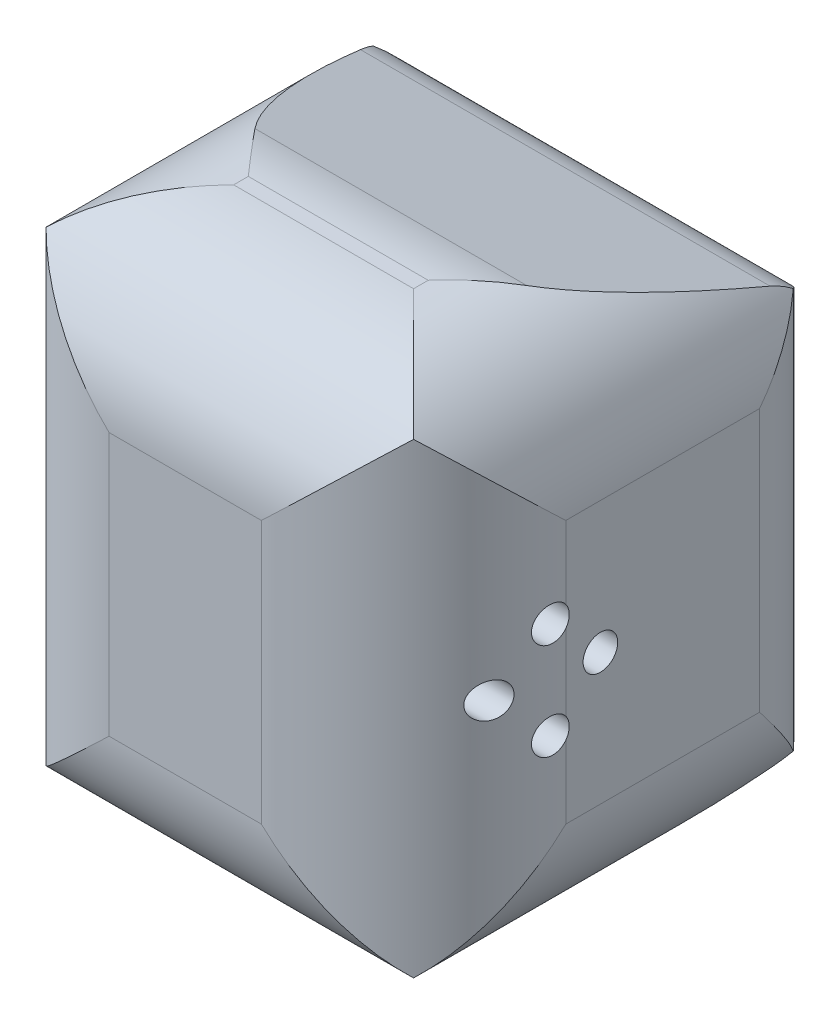
SolidWorks part; units mm, degrees
ref_plane "Front Plane" through (0, 0, 0) normal (0, 0, 1) x (1, 0, 0)
ref_plane "Top Plane" through (0, 0, 0) normal (0, 1, 0) x (1, 0, 0)
ref_plane "Right Plane" through (0, 0, 0) normal (1, 0, 0) x (0, 0, -1)
ref_plane "PX_m33_000" through (-33, 0, 0) normal (1, 0, 0) x (0, 0, -1)
sketch "S_prism1" plane through (-33, 0, 0) normal (1, 0, 0) x (0, 0, -1)
  line L0 (0, -20.5991) -> (0, 20.5991)
  line L1 (-7.0778, 30.1627) -> (-32.2859, 37.8651)
  line L2 (-39.8836, 39) -> (-42, 39)
  line L3 (-62, 19) -> (-62, -19)
  line L4 (-42, -39) -> (-39.8836, -39)
  line L5 (-32.2859, -37.8651) -> (-7.0778, -30.1627)
  arc A0 (-7.0778, -30.1627) -> (0, -20.5991) centre (-10.0001, -20.5991) ccw
  arc A1 (0, 20.5991) -> (-7.0778, 30.1627) centre (-10.0001, 20.5991) ccw
  arc A2 (-32.2859, 37.8651) -> (-39.8836, 39) centre (-39.8837, 12.9999) ccw
  arc A3 (-42, 39) -> (-62, 19) centre (-41.9999, 18.9999) ccw
  arc A4 (-62, -19) -> (-42, -39) centre (-41.9999, -18.9999) ccw
  arc A5 (-39.8836, -39) -> (-32.2859, -37.8651) centre (-39.8837, -12.9999) ccw
extrude "Boss_1" add sketch "S_prism1" along normal blind 66
ref_plane "PY_m40_000" through (0, -40, 0) normal (0, 1, 0) x (1, 0, 0)
sketch "S_pcut2" plane through (0, -40, 0) normal (0, 1, 0) x (1, 0, 0)
  line L0 (33.6, -62.6) -> (11, -62.6)
  line L1 (11, -62.6) -> (11, -62)
  line L2 (33, -40) -> (33.6, -40)
  line L3 (33.6, -40) -> (33.6, -62.6)
  arc A0 (11, -62) -> (33, -40) centre (10.9998, -39.9998) ccw
extrude "Cut_2" cut sketch "S_pcut2" along normal blind 80
sketch "S_pcut3" plane through (0, -40, 0) normal (0, 1, 0) x (1, 0, 0)
  line L0 (-33.6, -62.6) -> (-11, -62.6)
  line L1 (-11, -62.6) -> (-11, -62)
  line L2 (-33, -40) -> (-33.6, -40)
  line L3 (-33.6, -40) -> (-33.6, -62.6)
  arc A0 (-11, -62) -> (-33, -40) centre (-10.9998, -39.9998) cw
extrude "Cut_3" cut sketch "S_pcut3" along normal blind 80
sketch "S_pcut4" plane through (0, -40, 0) normal (0, 1, 0) x (1, 0, 0)
  line L0 (33.6, 0.6) -> (21, 0.6)
  line L1 (21, 0.6) -> (21, 0)
  line L2 (33, -12) -> (33.6, -12)
  line L3 (33.6, -12) -> (33.6, 0.6)
  arc A0 (21, 0) -> (33, -12) centre (21.0001, -11.9999) cw
extrude "Cut_4" cut sketch "S_pcut4" along normal blind 80 body kept at (-33, -30.1627, 7.0778)
sketch "S_pcut5" plane through (0, -40, 0) normal (0, 1, 0) x (1, 0, 0)
  line L0 (-33.6, 0.6) -> (-21, 0.6)
  line L1 (-21, 0.6) -> (-21, 0)
  line L2 (-33, -12) -> (-33.6, -12)
  line L3 (-33.6, -12) -> (-33.6, 0.6)
  arc A0 (-21, 0) -> (-33, -12) centre (-21.0001, -11.9999) ccw
extrude "Cut_5" cut sketch "S_pcut5" along normal blind 80
ref_plane "PZ_m0_100" through (0, 0, -0.1) normal (0, 0, 1) x (1, 0, 0)
sketch "S_pcut6" plane through (0, 0, -0.1) normal (0, 0, 1) x (1, 0, 0)
  line L0 (33.6, 39.6) -> (13, 39.6)
  line L1 (13, 39.6) -> (13, 39)
  line L2 (33, 19) -> (33.6, 19)
  line L3 (33.6, 19) -> (33.6, 39.6)
  arc A0 (13, 39) -> (33, 19) centre (12.9999, 18.9999) cw
extrude "Cut_6" cut sketch "S_pcut6" along normal blind 62.2
sketch "S_pcut7" plane through (0, 0, -0.1) normal (0, 0, 1) x (1, 0, 0)
  line L0 (33.6, -39.6) -> (13, -39.6)
  line L1 (13, -39.6) -> (13, -39)
  line L2 (33, -19) -> (33.6, -19)
  line L3 (33.6, -19) -> (33.6, -39.6)
  arc A0 (13, -39) -> (33, -19) centre (12.9999, -18.9999) ccw
extrude "Cut_7" cut sketch "S_pcut7" along normal blind 62.2
sketch "S_pcut8" plane through (0, 0, -0.1) normal (0, 0, 1) x (1, 0, 0)
  line L0 (-33.6, 39.6) -> (-13, 39.6)
  line L1 (-13, 39.6) -> (-13, 39)
  line L2 (-33, 19) -> (-33.6, 19)
  line L3 (-33.6, 19) -> (-33.6, 39.6)
  arc A0 (-13, 39) -> (-33, 19) centre (-12.9999, 18.9999) ccw
extrude "Cut_8" cut sketch "S_pcut8" along normal blind 62.2
sketch "S_pcut9" plane through (0, 0, -0.1) normal (0, 0, 1) x (1, 0, 0)
  line L0 (-33.6, -39.6) -> (-13, -39.6)
  line L1 (-13, -39.6) -> (-13, -39)
  line L2 (-33, -19) -> (-33.6, -19)
  line L3 (-33.6, -19) -> (-33.6, -39.6)
  arc A0 (-13, -39) -> (-33, -19) centre (-12.9999, -18.9999) cw
extrude "Cut_9" cut sketch "S_pcut9" along normal blind 62.2
sketch "S_cut10" plane through (0, 0, -0.1) normal (0, 0, 1) x (1, 0, 0)
  line L0 (-26, -24) -> (26, -24)
  line L1 (26, -24) -> (26, 24)
  line L2 (26, 24) -> (-26, 24)
  line L3 (-26, 24) -> (-26, -24)
  dimension "P1" = 26
  dimension "P2" = 24
  dimension "P3" = 26
  dimension "P4" = 24
  dimension "P5" = 26
  dimension "P6" = 24
  dimension "P7" = 26
  dimension "P8" = 24
extrude "Pocket_10" cut sketch "S_cut10" along normal blind 16.2
ref_plane "PZ_p16_000" through (0, 0, 16) normal (0, 0, 1) x (1, 0, 0)
sketch "S_cut11" plane through (0, 0, 16) normal (0, 0, 1) x (1, 0, 0)
  line L0 (-26, -30) -> (26, -30)
  line L1 (26, -30) -> (26, 30)
  line L2 (26, 30) -> (-26, 30)
  line L3 (-26, 30) -> (-26, -30)
  dimension "P1" = 26
  dimension "P2" = 30
  dimension "P3" = 26
  dimension "P4" = 30
  dimension "P5" = 26
  dimension "P6" = 30
  dimension "P7" = 26
  dimension "P8" = 30
extrude "Pocket_11" cut sketch "S_cut11" along normal blind 36
ref_plane "PZ_p51_900" through (0, 0, 51.9) normal (0, 0, 1) x (1, 0, 0)
sketch "S_cut12" plane through (0, 0, 51.9) normal (0, 0, 1) x (1, 0, 0)
  line L0 (-18, -24) -> (18, -24)
  line L1 (18, -24) -> (18, 24)
  line L2 (18, 24) -> (-18, 24)
  line L3 (-18, 24) -> (-18, -24)
  dimension "P1" = 18
  dimension "P2" = 24
  dimension "P3" = 18
  dimension "P4" = 24
  dimension "P5" = 18
  dimension "P6" = 24
  dimension "P7" = 18
  dimension "P8" = 24
extrude "Pocket_12" cut sketch "S_cut12" along normal blind 6.1
sketch "S_cut13" plane through (0, 0, 16) normal (0, 0, 1) x (1, 0, 0)
  line L0 (-33.1, -16) -> (-25.9, -16)
  line L1 (-25.9, -16) -> (-25.9, 16)
  line L2 (-25.9, 16) -> (-33.1, 16)
  line L3 (-33.1, 16) -> (-33.1, -16)
  dimension "P1" = 33.1
  dimension "P2" = 16
  dimension "P3" = 25.9
  dimension "P4" = 16
  dimension "P5" = 25.9
  dimension "P6" = 16
  dimension "P7" = 33.1
  dimension "P8" = 16
extrude "Pocket_13" cut sketch "S_cut13" along normal blind 28
ref_plane "PX_p25_900" through (25.9, 0, 0) normal (1, 0, 0) x (0, 0, -1)
sketch "S_hole14" plane through (25.9, 0, 0) normal (1, 0, 0) x (0, 0, -1)
  circle A0 centre (-49, 0) radius 2.5
  dimension "D1_S_hole14" = 5
  dimension "P2" = 49
extrude "Hole_14" cut sketch "S_hole14" along normal blind 7.2
sketch "S_hole15" plane through (25.9, 0, 0) normal (1, 0, 0) x (0, 0, -1)
  circle A0 centre (-42, 7) radius 2.5
  dimension "D1_S_hole15" = 5
  dimension "P2" = 42
  dimension "P3" = 7
extrude "Hole_15" cut sketch "S_hole15" along normal blind 7.2
sketch "S_hole16" plane through (25.9, 0, 0) normal (1, 0, 0) x (0, 0, -1)
  circle A0 centre (-42, -7) radius 2.5
  dimension "D1_S_hole16" = 5
  dimension "P2" = 42
  dimension "P3" = 7
extrude "Hole_16" cut sketch "S_hole16" along normal blind 7.2
sketch "S_hole17" plane through (25.9, 0, 0) normal (1, 0, 0) x (0, 0, -1)
  circle A0 centre (-35, 0) radius 2.5
  dimension "D1_S_hole17" = 5
  dimension "P2" = 35
extrude "Hole_17" cut sketch "S_hole17" along normal blind 7.2
ref_plane "PX_m33_100" through (-33.1, 0, 0) normal (1, 0, 0) x (0, 0, -1)
sketch "S_hole18" plane through (-33.1, 0, 0) normal (1, 0, 0) x (0, 0, -1)
  circle A0 centre (-8, -10) radius 1.2
  dimension "D1_S_hole18" = 2.4
  dimension "P2" = 8
  dimension "P3" = 10
extrude "Hole_18" cut sketch "S_hole18" along normal blind 7.2
sketch "S_hole19" plane through (-33.1, 0, 0) normal (1, 0, 0) x (0, 0, -1)
  circle A0 centre (-8, -10) radius 2.3
  dimension "D1_S_hole19" = 4.6
  dimension "P2" = 8
  dimension "P3" = 10
extrude "Hole_19" cut sketch "S_hole19" along normal blind 2
sketch "S_hole20" plane through (-33.1, 0, 0) normal (1, 0, 0) x (0, 0, -1)
  circle A0 centre (-8, 10) radius 1.2
  dimension "D1_S_hole20" = 2.4
  dimension "P2" = 8
  dimension "P3" = 10
extrude "Hole_20" cut sketch "S_hole20" along normal blind 7.2
sketch "S_hole21" plane through (-33.1, 0, 0) normal (1, 0, 0) x (0, 0, -1)
  circle A0 centre (-8, 10) radius 2.3
  dimension "D1_S_hole21" = 4.6
  dimension "P2" = 8
  dimension "P3" = 10
extrude "Hole_21" cut sketch "S_hole21" along normal blind 2
equation "\"plate_t\" = 3"
equation "\"clearance\" = 0.5"
